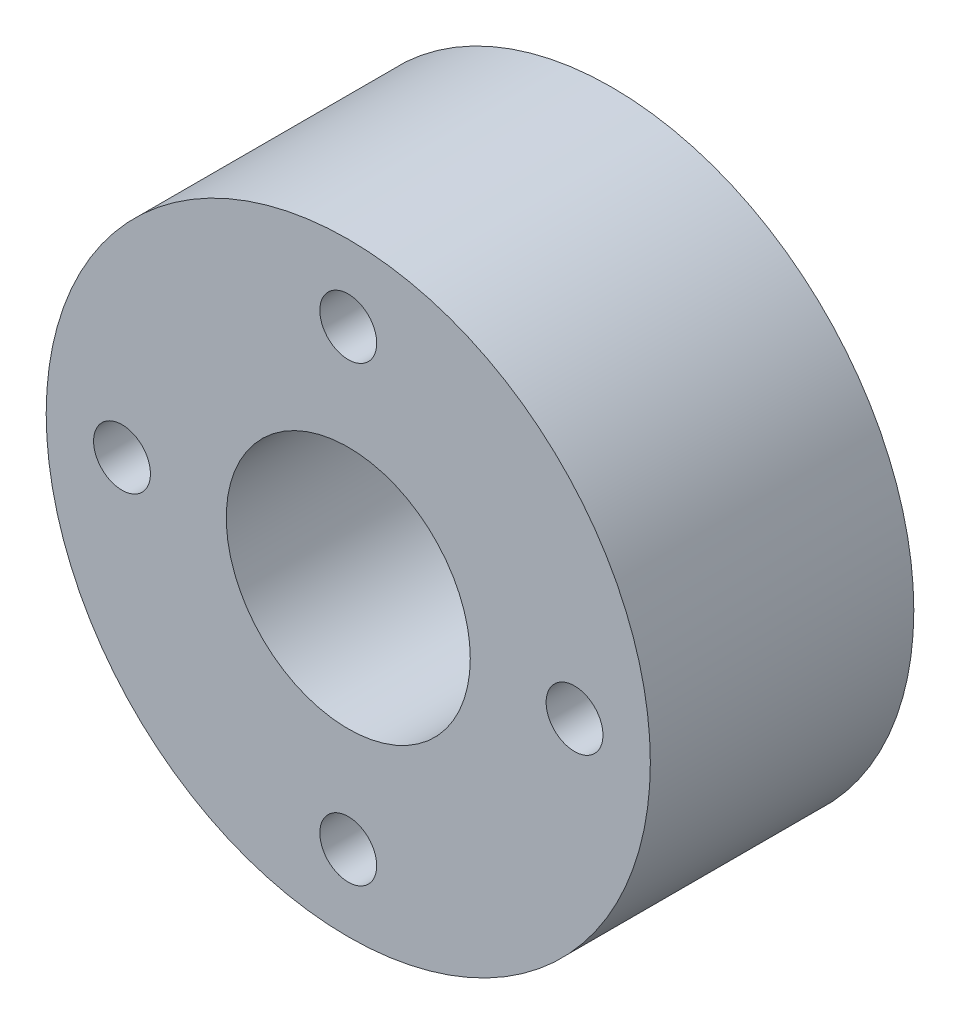
SolidWorks part; units mm, degrees
ref_plane "Front Plane" through (0, 0, 0) normal (0, 0, 1) x (1, 0, 0)
ref_plane "Top Plane" through (0, 0, 0) normal (0, 1, 0) x (1, 0, 0)
ref_plane "Right Plane" through (0, 0, 0) normal (1, 0, 0) x (0, 0, -1)
sketch "Sketch2" plane through (0, 0, 0) normal (0, 0, 1) x (1, 0, 0)
  circle A0 centre (0, 0) radius 15.9375
  circle A1 centre (0, 0) radius 7.9375
  dimension "D1" = 31.875
  dimension "D2" = 15.875
extrude "Boss-Extrude1" add sketch "Sketch2" along normal blind 13.9
sketch "Sketch3" plane through (0, 0, 0) normal (0, 0, -1) x (-1, 0, 0)
  circle A0 centre (0, 11.9375) radius 1.5
  circle A1 centre (11.9375, 0) radius 1.5
  circle A2 centre (0, -11.9375) radius 1.5
  circle A3 centre (-11.9375, 0) radius 1.5
  point P12 (0, 0)
  dimension "D2" = 3
  dimension "D1" = 11.9375
  dimension "D3" = 4
extrude "Cut-Extrude1" cut sketch "Sketch3" against normal through all
sketch "Sketch4" plane through (0, 0, 0) normal (0, 0, -1) x (-1, 0, 0)
  circle A0 centre (0, 11.9375) radius 2.75
  circle A1 centre (11.9375, 0) radius 2.75
  circle A2 centre (0, -11.9375) radius 2.75
  circle A3 centre (-11.9375, 0) radius 2.75
  dimension "D1" = 5.5
extrude "Cut-Extrude2" cut sketch "Sketch4" against normal blind 5.5
sketch "Sketch5" plane through (0, 0, 13.9) normal (0, 0, 1) x (1, 0, 0)
  circle A0 centre (0, 0) radius 7.9375
  circle A1 centre (0, 0) radius 6.4375
  circle A2 centre (0, 0) radius 7.9375 construction
  dimension "D1" = 1.5
extrude "Boss-Extrude2" add sketch "Sketch5" against normal through all
sketch "Sketch6" plane through (0, 0, 0) normal (0, 0, -1) x (-1, 0, 0)
  circle A0 centre (0, 0) radius 7.9375 construction
  circle A1 centre (0, 0) radius 6.4375 construction
  circle A2 centre (0, 0) radius 7.9375
  circle A3 centre (0, 0) radius 6.4375
extrude "Cut-Extrude3" cut sketch "Sketch6" against normal blind 2.8578
